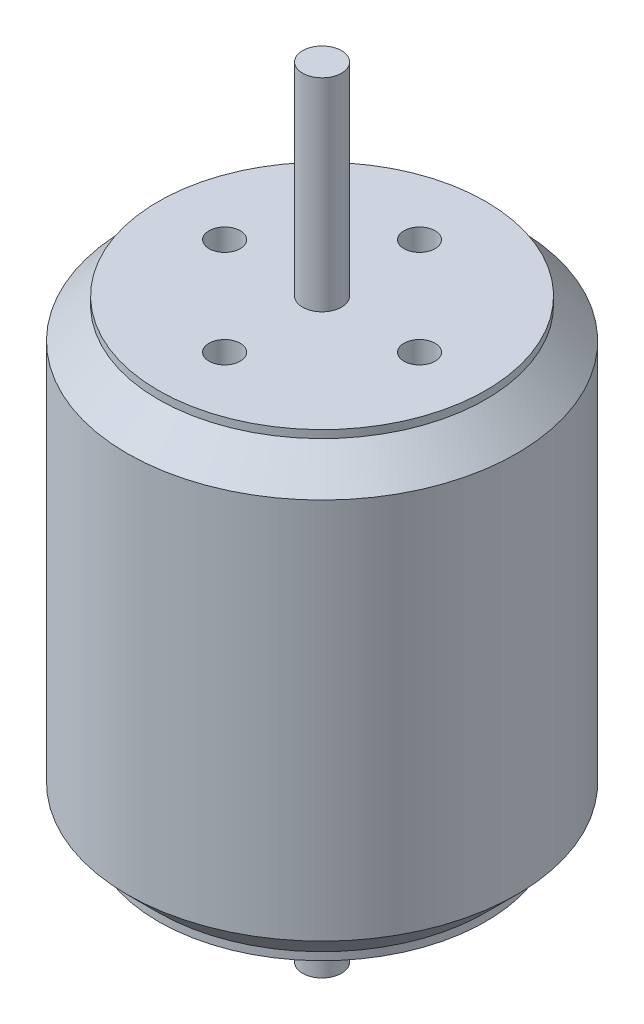
SolidWorks part; units mm, degrees
ref_plane "Front Plane" through (0, 0, 0) normal (0, 0, 1) x (1, 0, 0)
ref_plane "Top Plane" through (0, 0, 0) normal (0, 1, 0) x (1, 0, 0)
ref_plane "Right Plane" through (0, 0, 0) normal (1, 0, 0) x (0, 0, -1)
sketch "Sketch1" plane through (0, 0, 0) normal (0, 1, 0) x (1, 0, 0)
  line L0 (0, 0) -> (-12.5, 0) construction
  circle A0 centre (0, 0) radius 25
  circle A1 centre (0, 0) radius 2.5
  circle A2 centre (-12.5, 0) radius 2
  circle A3 centre (0, 12.5) radius 2
  circle A4 centre (12.5, 0) radius 2
  circle A5 centre (0, -12.5) radius 2
  circle A6 centre (0, 0) radius 21
  point P15 (0, 0)
  dimension "D1" = 5
  dimension "D2" = 50
  dimension "D3" = 4
  dimension "D4" = 12.5
  dimension "D6" = 4
  dimension "D5" = 4
extrude "Boss-Extrude1" add sketch "Sketch1" against normal blind 59 contours A1 | A6 A1 A2 A3 A4 A5 | A2 | A3 | A4 | A5 region at (0, 0, 0) region at (-12.5, 0, 0) region at (0, 0, -12.5) region at (12.5, 0, 0) region at (0, 0, 12.5) region at (-20.406, 0, 0)
extrude "Boss-Extrude2" add sketch "Sketch1<3>" along normal blind 26 contours A1 region at (0, 0, 0)
sketch "Sketch1<3>" plane through (0, 0, 0) normal (0, 1, 0) x (1, 0, 0) same geometry as "Sketch1"
extrude "Cut-Extrude1" cut sketch "Sketch1<4>" against normal blind 10 contours A2 | A3 | A4 | A5 region at (-12.5, 0, 0) region at (0, 0, -12.5) region at (12.5, 0, 0) region at (0, 0, 12.5)
sketch "Sketch1<4>" plane through (0, 0, 0) normal (0, 1, 0) x (1, 0, 0) same geometry as "Sketch1"
extrude "Boss-Extrude3" add sketch "Sketch1<5>" against normal offset from surface (49 mm away) 5 from offset 5 contours A0 A6 region at (-24.2929, 0, 0) up to face at (0, -59, 21) offset against normal yes
sketch "Sketch1<5>" plane through (0, 0, 0) normal (0, 1, 0) x (1, 0, 0) same geometry as "Sketch1"
chamfer "Chamfer1" distance 4 angle 45 2 edges at (0, -5, 21) (0, -54, 21)
extrude "Boss-Extrude4" add sketch "Sketch1<6>" against normal blind 15 from surface contours A1 region at (0, 0, 0) starting at face at (0, -59, 21)
sketch "Sketch1<6>" plane through (0, 0, 0) normal (0, 1, 0) x (1, 0, 0) same geometry as "Sketch1"
